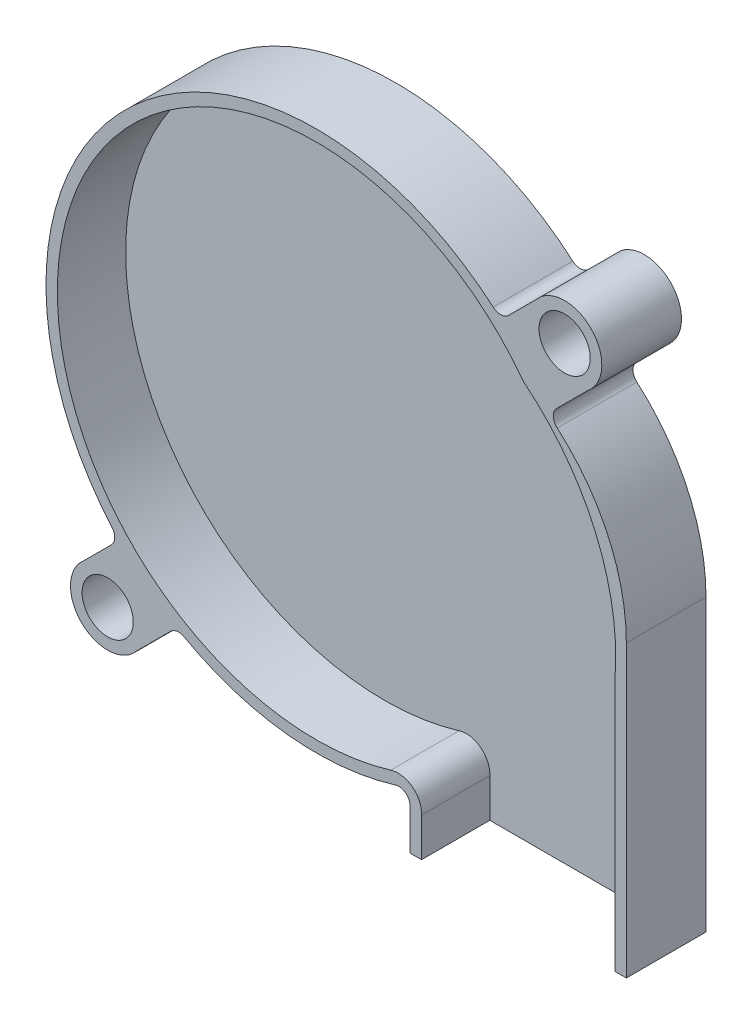
SolidWorks part; units mm, degrees
ref_plane "Płaszczyzna przednia" through (0, 0, 0) normal (0, 0, 1) x (1, 0, 0)
ref_plane "Płaszczyzna górna" through (0, 0, 0) normal (0, 1, 0) x (1, 0, 0)
ref_plane "Płaszczyzna prawa" through (0, 0, 0) normal (1, 0, 0) x (0, 0, -1)
sketch "Sketch1" plane through (0, 0, 0) normal (0, 0, 1) x (1, 0, 0)
  line L0 (3.5646, 25.5) -> (47.4354, 25.5) construction
  line L1 (0, 0) -> (51, 0) construction
  line L2 (0, 0) -> (0, 51) construction
  line L3 (0, 51) -> (51, 51) construction
  line L4 (51, 0) -> (51, 51) construction
  line L5 (0, 0) -> (51, 51) construction
  line L6 (0, 51) -> (51, 0) construction
  line L7 (51, 0) -> (51, 25.5)
  line L8 (51, 0) -> (32, 0)
  line L9 (32, 0) -> (32, 4.9789)
  line L10 (1.9724, 6.5686) -> (44.4314, 49.0276) construction
  line L11 (6.5686, 1.9724) -> (49.0276, 44.4314) construction
  line L12 (6.4171, 11.0133) -> (2.8815, 7.4777)
  line L13 (11.4995, 6.9033) -> (7.964, 3.3678)
  line L14 (44.0967, 39.5005) -> (47.6322, 43.036)
  line L15 (39.9867, 44.5829) -> (43.5223, 48.1185)
  arc A0 (44.1043, 39.4878) -> (44.0967, 39.5005) centre (23.75, 27.25) ccw
  arc A1 (51, 25.5) -> (44.1043, 39.4878) centre (33.3651, 25.5) ccw
  arc A2 (2.8815, 7.4777) -> (7.964, 3.3678) centre (5.4227, 5.4227) ccw
  arc A3 (43.5223, 48.1185) -> (47.6322, 43.036) centre (45.5773, 45.5773) cw
  arc A4 (39.9867, 44.5829) -> (6.4171, 11.0133) centre (23.75, 27.25) ccw
  arc A5 (11.4995, 6.9033) -> (32, 4.9789) centre (23.75, 27.25) ccw
  point P4 (25.5, 25.5)
  point P11 (25.5, 25.5)
  point P18 (23.2019, 27.7981)
  dimension "D2" = 47.5
  dimension "D1" = 51
  dimension "D3" = 19
  dimension "D5" = 3.25
  dimension "D6" = 5
  dimension "D7" = 5
extrude "Boss-Extrude1" add sketch "Sketch1" along normal blind 7
fillet "Fillet1" radius 1 4 edges at (44.1005, 39.4942, 0) (44.1005, 39.4942, 7) (44.0967, 39.5005, 3.5) (44.1043, 39.4878, 3.5)
fillet "Fillet2" radius 1 3 edges at (6.4171, 11.0133, 3.5) (11.4995, 6.9033, 3.5) (39.9867, 44.5829, 3.5)
fillet "Fillet3" radius 1 1 edges at (32, 4.9789, 3.5)
sketch "Sketch2" plane through (0, 0, 7) normal (0, 0, 1) x (1, 0, 0)
  line L0 (33, 0) -> (33, 3.3898)
  line L1 (33, 0) -> (50, 0)
  line L2 (50, 0) -> (50, 22.2175)
  line L3 (32, 3.5857) -> (32, 0) construction
  line L4 (32, 0) -> (51, 0) construction
  line L5 (51, 0) -> (51, 25.5) construction
  arc A0 (41.9923, 40.8434) -> (30.2867, 5.4593) centre (23.75, 27.25) ccw
  arc A2 (50, 22.2175) -> (41.9923, 40.8434) centre (28.3603, 23.9484) ccw
  arc A3 (33, 3.3898) -> (30.2867, 5.4593) centre (30.9468, 3.5114) ccw
  arc A5 (39.296, 45.205) -> (5.795, 11.704) centre (23.75, 27.25) ccw construction
  dimension "D1" = 22.75
  dimension "D3" = 1
  dimension "D2" = 1
extrude "Cut-Extrude1" cut sketch "Sketch2" against normal blind 6
sketch "Sketch3" plane through (0, 0, 1) normal (0, 0, 1) x (1, 0, 0)
  circle A0 centre (23.75, 27.25) radius 16
  arc A1 (41.9923, 40.8434) -> (30.2867, 5.4593) centre (23.75, 27.25) ccw construction
  dimension "D1" = 32
hole_wizard "Ø4.0mm Dowel Hole1" positions "Sketch6" profile "Sketch5" hole size "Ø4.0" standard "ANSI Metric" end condition through all
sketch "Sketch6" plane through (0, 0, 0) normal (0, 0, -1) x (-1, 0, 0)
  line L0 (-5.7461, 10.3423) -> (-2.8815, 7.4777) construction
  line L1 (-43.5223, 48.1185) -> (-40.6577, 45.2539) construction
  arc A0 (-7.964, 3.3678) -> (-2.8815, 7.4777) centre (-5.4227, 5.4227) ccw construction
  arc A3 (-43.5223, 48.1185) -> (-47.6322, 43.036) centre (-45.5773, 45.5773) ccw construction
  point P0 (-5.4227, 5.4227)
  point P2 (-45.5773, 45.5773)
  dimension "D1" = 6.5181
  dimension "D2" = 3.25
  dimension "D3" = 0
sketch "Sketch5" plane through (5.4227, 5.4227, 0) normal (1, 0, 0) x (0, 1, 0)
  line L0 (0, 0) -> (0, 7)
  line L1 (0, 7) -> (2.25, 7)
  line L2 (2.25, 7) -> (2.25, 0)
  line L5 (2.25, 0) -> (0, 0)
  line L11 (0, -6.35) -> (0, 107.95) construction
  dimension "Thru Hole Dia." = 4.5
  dimension "Thru Hole Depth" = 7
